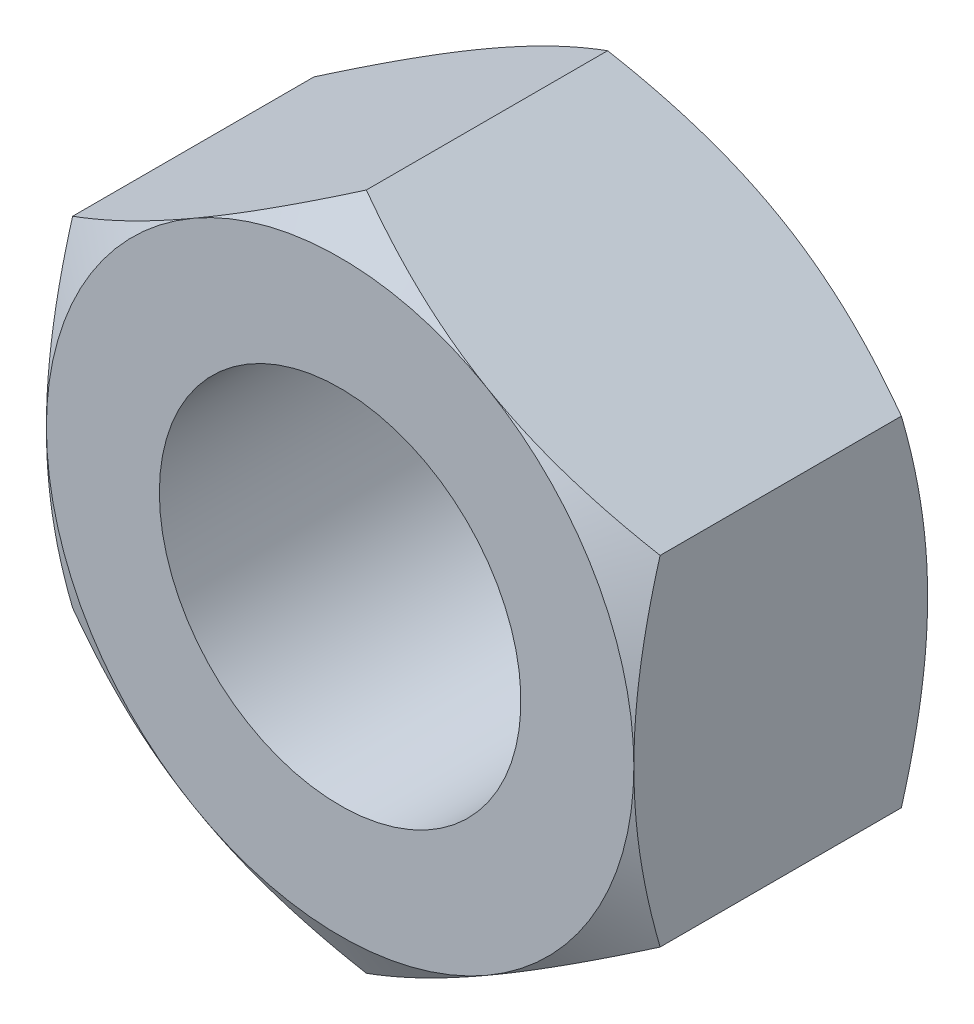
SolidWorks part; units mm, degrees
ref_plane "Front" through (0, 0, 0) normal (0, 0, 1) x (1, 0, 0)
ref_plane "Top" through (0, 0, 0) normal (0, 1, 0) x (1, 0, 0)
ref_plane "Right" through (0, 0, 0) normal (1, 0, 0) x (0, 0, -1)
sketch "Sketch1" plane through (0, 0, 0) normal (0, 0, 1) x (1, 0, 0)
  line L1 (-6.5, 3.7528) -> (-6.5, -3.7528)
  line L2 (-6.5, -3.7528) -> (0, -7.5056)
  line L3 (0, -7.5056) -> (6.5, -3.7528)
  line L4 (6.5, -3.7528) -> (6.5, 3.7528)
  line L5 (6.5, 3.7528) -> (0, 7.5056)
  line L6 (0, 7.5056) -> (-6.5, 3.7528)
  circle A0 centre (0, 0) radius 6.5 construction
  circle A1 centre (0, 0) radius 4 construction
  point P10 (0, 4)
  dimension "hex" = 13
  dimension "dia" = 8
extrude "Extrude1" add sketch "Sketch1" along normal mid plane 6.5
sketch "Sketch4" plane through (0, 0, -3.25) normal (0, 0, -1) x (-1, 0, 0)
  circle A0 centre (0, 0) radius 4 construction
  circle A1 centre (0, 0) radius 4
sketch "Sketch10" plane through (0, 0, 3.25) normal (0, 0, 1) x (1, 0, 0)
  circle A0 centre (0, 0) radius 4 construction
  circle A1 centre (0, 0) radius 4
extrude "Cut-Extrude2" [suppressed] cut sketch "Sketch10" against normal through all draft 45
sketch "Sketch11" plane through (0, 0, -3.25) normal (0, 0, -1) x (-1, 0, 0)
  circle A0 centre (0, 0) radius 4 construction
  circle A1 centre (0, 0) radius 4
extrude "Cut-Extrude3" [suppressed] cut sketch "Sketch11" against normal through all draft 45
sketch "Sketch13" plane through (0, 0, -3.25) normal (0, 0, -1) x (-1, 0, 0)
  circle A0 centre (0, 0) radius 4 construction
  circle A1 centre (0, 0) radius 4
extrude "Boss-Extrude1" add sketch "Sketch13" against normal up to vertex (6.5 mm away) separate body up to point (-6.5, 3.7528, 3.25)
curve "Helix/Spiral3" [suppressed] pitch 1.25 height 6.5 turns 5.2
sketch "Sketch12" plane through (0, 0, 0) normal (1, 0, 0) x (0, 0, -1)
  line L0 (4.3438, 4) -> (3.25, 4)
  line L1 (4.3438, 4) -> (3.875, 3.1881)
  line L2 (3.875, 3.1881) -> (3.7188, 3.1881)
  line L3 (3.7188, 3.1881) -> (3.25, 4)
  line L4 (3.7969, 3.1881) -> (3.7969, 4) construction
  line L5 (3.4844, 3.5941) -> (4.1094, 3.5941) construction
  dimension "D1" = 60
  dimension "D2" = 0.1562
  dimension "D3" = 0.625
sweep "Cut-Sweep1" [suppressed] cut profiles "Sketch12" path "Helix/Spiral3"
combine bodies "Combine1" operation type subtract main body 108 bodies to subtract 117
sketch "Sketch7" plane through (0, 0, 3.25) normal (0, 0, 1) x (1, 0, 0)
  circle A0 centre (0, 0) radius 6.5 construction
  circle A1 centre (0, 0) radius 6.5
extrude "Extrude2" cut sketch "Sketch7" against normal blind 25.4 draft 60 flip side to cut
mirror "Mirror2" about plane through (0, 0, 0) normal (0, 0, 1) of "Extrude2"
sketch "Sketch8" plane through (0, 0, 3.25) normal (0, 0, 1) x (1, 0, 0)
  line L0 (-2.8284, 2.8284) -> (0, 0) construction
  line L1 (0, -4.0599) -> (0, 4.0599) construction
  circle A1 centre (0, 0) radius 4 construction
  point P0 (-2.8284, 2.8284)
  dimension "D1" = 45
sketch "Sketch14" plane through (0, 0, 3.25) normal (0, 0, 1) x (1, 0, 0)
  line L0 (0, 0) -> (-4, 0) construction
  circle A0 centre (0, 0) radius 4 construction
equation "\"D3@Helix/Spiral3\" = \"length@Extrude1\" "
equation "\"D2@Sketch12\" = \"D4@Helix/Spiral3\"*.125"
equation "\"D3@Sketch12\" = \"D4@Helix/Spiral3\"*.50"
